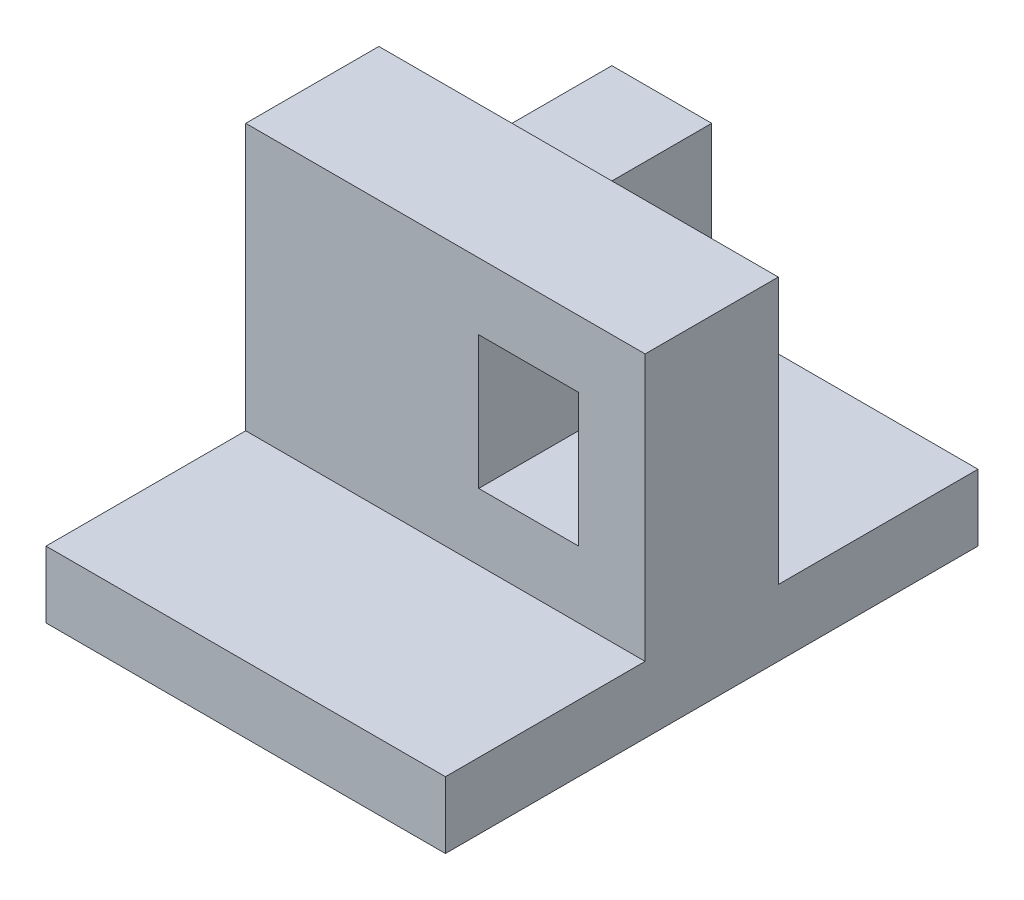
SolidWorks part; units mm, degrees
ref_plane "Front Plane" through (0, 0, 0) normal (0, 0, 1) x (1, 0, 0)
ref_plane "Top Plane" through (0, 0, 0) normal (0, 1, 0) x (1, 0, 0)
ref_plane "Right Plane" through (0, 0, 0) normal (1, 0, 0) x (0, 0, -1)
sketch "Sketch1" plane through (0, 0, 0) normal (0, 0, 1) x (1, 0, 0)
  line L1 (-60, 0) -> (0, 0)
  line L2 (-60, 0) -> (-60, 10)
  line L3 (-60, 10) -> (0, 10)
  line L4 (0, 0) -> (0, 10)
  line L5 (-60, 10) -> (0, 10)
  line L6 (-60, 10) -> (-60, 50)
  line L7 (-60, 50) -> (0, 50)
  line L8 (0, 10) -> (0, 50)
  line L9 (-25, 40) -> (-10, 40)
  line L10 (-25, 40) -> (-25, 20)
  line L11 (-25, 20) -> (-10, 20)
  line L12 (-10, 40) -> (-10, 20)
  line L13 (-35, 40) -> (-50, 40)
  line L14 (-35, 40) -> (-35, 20)
  line L15 (-35, 20) -> (-50, 20)
  line L16 (-50, 40) -> (-50, 20)
  point P15 (-35, 20)
  dimension "D1" = 60
  dimension "D2" = 50
  dimension "D3" = 10
  dimension "D4" = 10
  dimension "D5" = 20
  dimension "D6" = 15
  dimension "D7" = 10
  dimension "D8" = 15
  dimension "D9" = 10
  dimension "D10" = 20
extrude "Boss-Extrude2" add sketch "Sketch1" along normal blind 30 and the other way blind 50 contours L1 L4 L3 L2 region at (-30, 5, 0)
extrude "Boss-Extrude3" add sketch "Sketch1<4>" against normal blind 20 contours L3 L8 L7 L6 L16 L13 L14 L15 L9 L12 L11 L10 region at (-30, 30, 0)
sketch "Sketch1<4>" plane through (0, 0, 0) normal (0, 0, 1) x (1, 0, 0) same geometry as "Sketch1"
extrude "Boss-Extrude4" add sketch "Sketch1<5>" against normal blind 45 contours L13 L16 L15 L14 region at (-42.5, 30, 0)
sketch "Sketch1<5>" plane through (0, 0, 0) normal (0, 0, 1) x (1, 0, 0) same geometry as "Sketch1"
